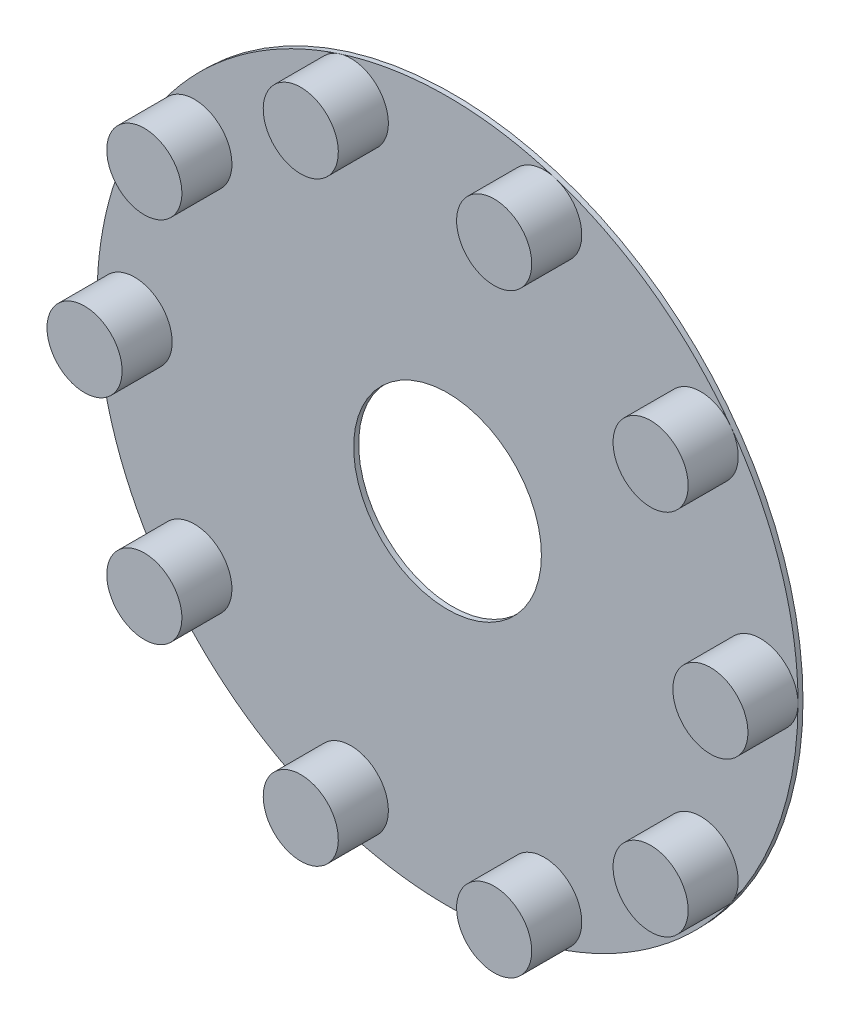
SolidWorks part; units mm, degrees
ref_plane "前视基准面" through (0, 0, 0) normal (0, 0, 1) x (1, 0, 0)
ref_plane "上视基准面" through (0, 0, 0) normal (0, 1, 0) x (1, 0, 0)
ref_plane "右视基准面" through (0, 0, 0) normal (1, 0, 0) x (0, 0, -1)
other "Configuration Table"
ref_axis "基准轴1" through (0, 0, 55) along (0, 0, -1)
sketch "PinsBaseSketch" plane through (0, 0, 0) normal (0, 0, 1) x (1, 0, 0)
  circle A0 centre (0, 0) radius 28
extrude "PinsBaseExtrude" add sketch "PinsBaseSketch" along normal blind 0.2 and the other way blind 0.2
sketch "PinsSketch" plane through (0, 0, 0) normal (0, 0, 1) x (1, 0, 0)
  circle A0 centre (25, 0) radius 3
extrude "PinsExtrude" add sketch "PinsSketch" along normal blind 4.2 and the other way blind 0.2
pattern_circular "PinsPattern" count 10 every 36 about axis through (0, 0, 55) along (0, 0, -1) of "PinsExtrude"
sketch "BoreRevolveSketch" plane through (0, 0, 0) normal (1, 0, 0) x (0, 0, -1)
  line L0 (0, 0) -> (1, 0) construction
  line L1 (-2, 0) -> (2, 0)
  line L2 (2, 0) -> (2, 7.5)
  line L3 (2, 7.5) -> (-2, 7.5)
  line L4 (-2, 7.5) -> (-2, 0)
  dimension "TaperSide1" = 7.5
  dimension "TaperSide2" = 7.5
revolve "BoreRevolveCut" cut sketch "BoreRevolveSketch" angle 360 about L0
